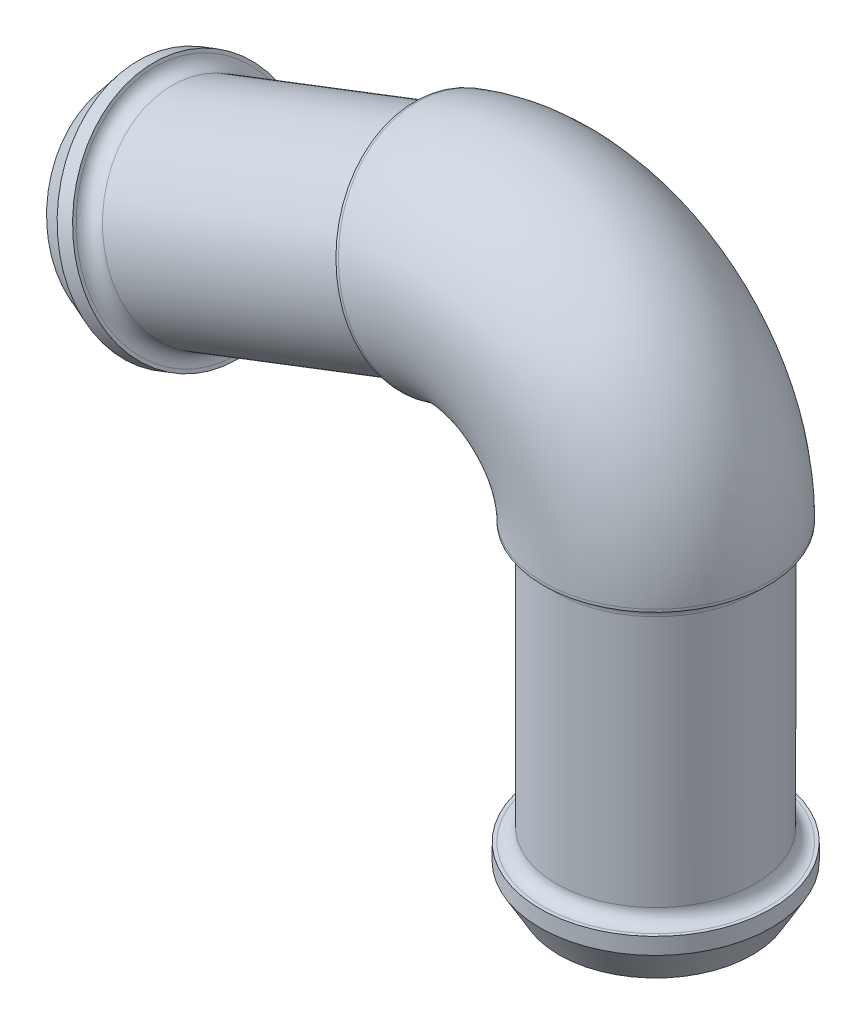
SolidWorks part; units mm, degrees
material "ABS"
ref_plane "X-Y Datum" through (0, 0, 0) normal (0, 0, 1) x (1, 0, 0)
ref_plane "X-Z Datum" through (0, 0, 0) normal (0, 1, 0) x (1, 0, 0)
ref_plane "Y-Z Datum" through (0, 0, 0) normal (1, 0, 0) x (0, 0, -1)
sketch3d "3DSketch4"
  line L0 (0, 0, 0) -> (0, 31.75, 0)
  line L1 (-48.6532, 33.4384, 0) -> (-19.012, 44.8166, 0)
  arc A0 (0, 31.75, 0) -> (-19.012, 44.8166, 0) centre (-13.9962, 31.75, 0) ccw
  point P6 (-13.9962, 31.75, 13.9962)
  dimension "D1" = 69
  dimension "D4" = 13.9962
  dimension "D2" = 31.75
  dimension "D3" = 31.75
sweep "Sweep1" add path "3DSketch4" circular profile diameter 19.05 parameters "D3"=19.05
sketch3d "3DSketch5"
  line L0 (-19.2492, 44.7256, 0) -> (-19.012, 44.8166, 0)
  line L1 (-48.6532, 33.4384, 0) -> (-19.012, 44.8166, 0) construction
  line L2 (0, 31.496, 0) -> (0, 31.75, 0)
  line L3 (0, 0, 0) -> (0, 31.75, 0) construction
  arc A0 (0, 31.75, 0) -> (-19.012, 44.8166, 0) centre (-13.9962, 31.75, 0) ccw construction
  arc A1 (0, 31.75, 0) -> (-19.012, 44.8166, 0) centre (-13.9962, 31.75, 0) ccw
  point P13 (-13.9962, 31.75, 13.9962)
  point P14 (-13.9962, 31.75, 13.9962)
  dimension "D1" = 0.254
  dimension "D2" = 0.254
sweep "Sweep2" add path "3DSketch5" circular profile diameter 21.59 parameters "D3"=21.59
sweep "Cut-Sweep1" cut path "3DSketch4<4>" circular profile diameter 15.875 parameters "D3"=15.875
sketch3d "3DSketch4<4>" same geometry as "3DSketch4"
sketch "Sketch1" plane through (-31.2175, -11.9833, 0) normal (-0.9336, -0.3584, 0) x (0, 0, 1)
  circle A0 centre (0, 48.6532) radius 9.525 construction
  circle A1 centre (0, 48.6532) radius 9.525
  circle A3 centre (0, 48.6532) radius 11.1125
  dimension "D1" = 22.225
extrude "Boss-Extrude1" add sketch "Sketch1" against normal blind 4.7625
sketch "Sketch2" plane through (0, 0, 0) normal (0, -1, 0) x (1, 0, 0)
  circle A0 centre (0, 0) radius 9.525 construction
  circle A1 centre (0, 0) radius 9.525
  circle A3 centre (0, 0) radius 11.1125
  dimension "D1" = 22.225
extrude "Boss-Extrude2" add sketch "Sketch2" against normal blind 4.7625
chamfer "Chamfer1" distance 3.175 angle 30 2 edges at (0, 0, -11.1125) (-44.6709, 23.064, 0) first distance on face at (0, 4.7625, -11.1125) first distance on face at (-40.2247, 24.7708, 0)
fillet "Fillet1" radius 1.27 2 edges at (-40.7936, 26.2528, 0) (0, 4.7625, -9.525)
fillet "Fillet2" radius 1.27 2 edges at (0, 31.496, 9.525) (-15.8357, 35.8332, 0)
